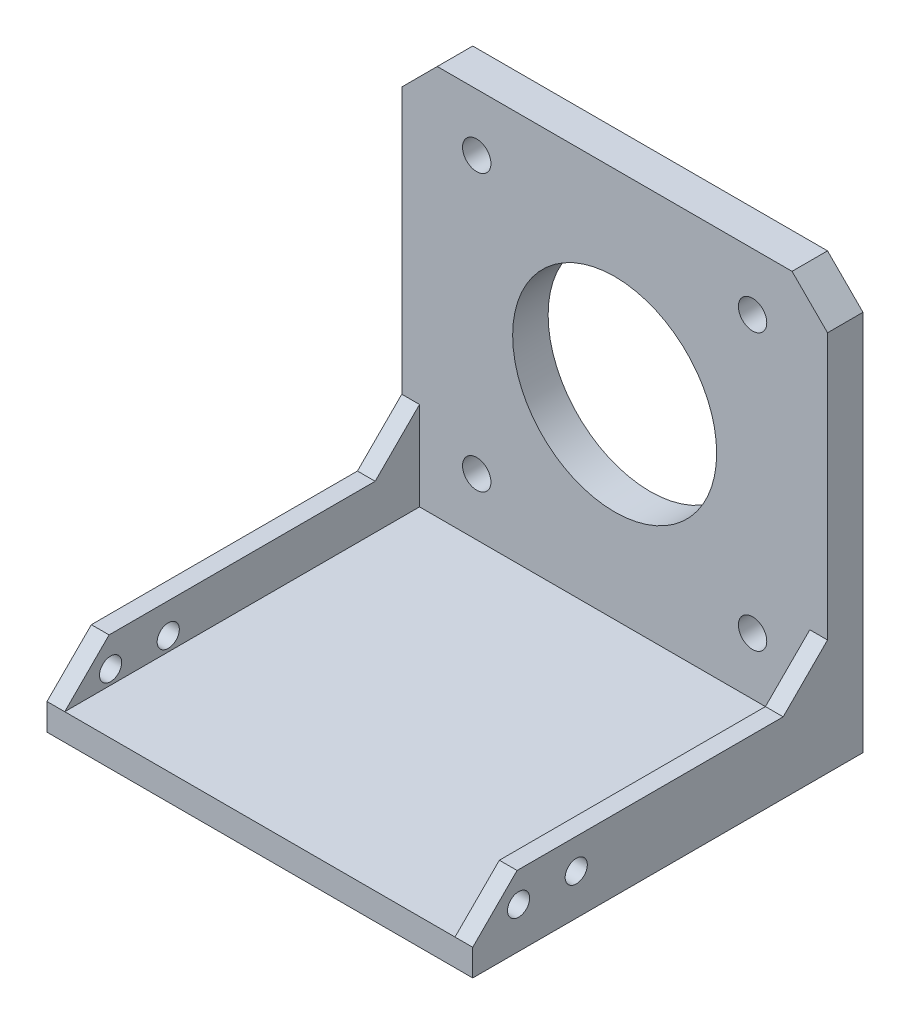
SolidWorks part; units mm, degrees
ref_plane "Ebene vorne" through (0, 0, 0) normal (0, 0, 1) x (1, 0, 0)
ref_plane "Ebene oben" through (0, 0, 0) normal (0, 1, 0) x (1, 0, 0)
ref_plane "Ebene rechts" through (0, 0, 0) normal (1, 0, 0) x (0, 0, -1)
sketch "Skizze1" plane through (0, 0, 0) normal (0, 1, 0) x (1, 0, 0)
  line L1 (24, 22) -> (-24, 22)
  line L2 (24, 22) -> (24, -22)
  line L3 (24, -22) -> (-24, -22)
  line L4 (-24, 22) -> (-24, -22)
  line L5 (24, 22) -> (-24, -22) construction
  line L6 (24, -22) -> (-24, 22) construction
  point P0 (0, 0)
  dimension "D1" = 48
  dimension "D2" = 44
extrude "Aufsatz-Linear austragen1" add sketch "Skizze1" along normal blind 3
sketch "Skizze2" plane through (0, 3, 0) normal (0, 1, 0) x (1, 0, 0)
  line L0 (24, -22) -> (24, 22) construction
  line L1 (-24, 22) -> (24, 22)
  line L2 (-24, 22) -> (-24, 18)
  line L3 (-24, 18) -> (24, 18)
  line L4 (24, 22) -> (24, 18)
  dimension "D1" = 4
extrude "Aufsatz-Linear austragen2" add sketch "Skizze2" along normal blind 44
sketch "Skizze3" plane through (0, 0, -18) normal (0, 0, 1) x (1, 0, 0)
  line L0 (0, 47) -> (0, 3) construction
  line L1 (-24, 47) -> (24, 47) construction
  line L2 (-24, 3) -> (24, 3) construction
  line L4 (-15.55, 40.55) -> (15.55, 40.55) construction
  line L5 (-15.55, 40.55) -> (-15.55, 9.45) construction
  line L6 (-15.55, 9.45) -> (15.55, 9.45) construction
  line L7 (15.55, 40.55) -> (15.55, 9.45) construction
  line L8 (-15.55, 40.55) -> (15.55, 9.45) construction
  line L9 (-15.55, 9.45) -> (15.55, 40.55) construction
  circle A0 centre (0, 25) radius 11.5
  circle A1 centre (-15.55, 40.55) radius 1.6
  circle A2 centre (15.55, 40.55) radius 1.6
  circle A3 centre (15.55, 9.45) radius 1.6
  circle A4 centre (-15.55, 9.45) radius 1.6
  dimension "D1" = 23
  dimension "D3" = 3.2
  dimension "D2" = 31.1
extrude "Schnitt-Linear austragen1" cut sketch "Skizze3" against normal through all
sketch "Skizze5" plane through (0, 3, 0) normal (0, 1, 0) x (1, 0, 0)
  line L1 (-24, 18) -> (-22, 18)
  line L2 (-24, 18) -> (-24, -22)
  line L3 (-24, -22) -> (-22, -22)
  line L4 (-22, 18) -> (-22, -22)
  line L5 (24, 18) -> (22, 18)
  line L6 (24, 18) -> (24, -22)
  line L7 (24, -22) -> (22, -22)
  line L8 (22, 18) -> (22, -22)
  line L10 (-24, -22) -> (24, -22) construction
  dimension "D2" = 2
extrude "Aufsatz-Linear austragen3" add sketch "Skizze5" along normal blind 5
chamfer "Fase2" distance 5 angle 45 4 edges at (23, 8, -18) (-23, 8, 22) (-23, 8, -18) (23, 8, 22)
chamfer "Fase3" distance 4 angle 45 2 edges at (24, 47, -20) (-24, 47, -20)
sketch "Skizze7" plane through (0, 0, 0) normal (0, -1, 0) x (1, 0, 0)
  line L0 (-1.75, 22) -> (1.75, 22)
  line L1 (-1, 17.2) -> (-1.75, 17.95)
  line L2 (-1.75, 17.95) -> (-1.75, 22)
  line L3 (-24, 22) -> (24, 22) construction
  line L4 (1, 17.2) -> (1.75, 17.95)
  line L5 (1.75, 17.95) -> (1.75, 22)
  line L6 (1, 17.2) -> (-1, 17.2)
  line L7 (-1.75, 17.95) -> (1.75, 17.95) construction
  line L8 (1, 17) -> (-1, 17) construction
  point P4 (0, 17.2)
  point P10 (0, 0)
  point P12 (0, 0)
  point P13 (0, 22)
  point P14 (1.8022, 22)
  point P15 (0, 0)
  point P16 (0, 22)
  point P17 (1.7336, 17.9048)
  point P18 (0, 17.95)
  dimension "D1" = 0.2
  dimension "D2" = 3.5
  dimension "D3" = 2
  dimension "D4" = 45
extrude "Aufsatz-Linear austragen4" add sketch "Skizze7" along normal blind 2
chamfer "Fase4" distance 2 angle 45 2 edges at (0, -2, 17.2) (0, -2, 22)
sketch "Skizze8" plane through (-24, 0, 0) normal (-1, 0, 0) x (0, 0, 1)
  line L0 (-22, 4.6) -> (20.4, 4.6) construction
  line L1 (-22, 43) -> (-22, 0) construction
  line L2 (22, 3) -> (17, 8) construction
  line L3 (-22, 0) -> (22, 0) construction
  circle A0 centre (16.83, 4.6) radius 1.25
  circle A1 centre (10.33, 4.6) radius 1.25
  point P12 (15.1315, 4.6)
  point P13 (0, 0)
  point P14 (0, 0)
  dimension "D4" = 2.5
  dimension "D1" = 4.6
  dimension "D2" = 3.57
  dimension "D3" = 6.5
extrude "Schnitt-Linear austragen2" cut sketch "Skizze8" against normal through all
